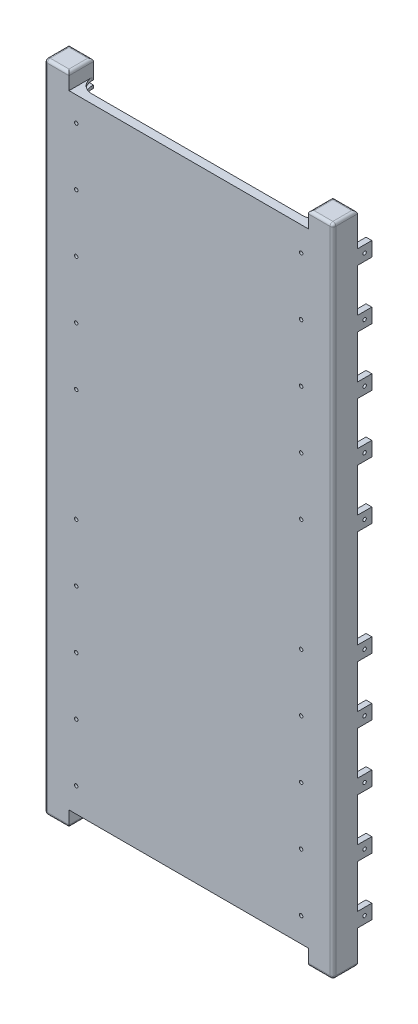
SolidWorks part; units mm, degrees
ref_plane "Front Plane" through (0, 0, 0) normal (0, 0, 1) x (1, 0, 0)
ref_plane "Top Plane" through (0, 0, 0) normal (0, 1, 0) x (1, 0, 0)
ref_plane "Right Plane" through (0, 0, 0) normal (1, 0, 0) x (0, 0, -1)
sketch "Sketch1" plane through (0, 0, 0) normal (0, 1, 0) x (1, 0, 0)
  line L1 (-3.25, -4.25) -> (4.25, -4.25)
  line L2 (-4.25, -3.25) -> (-4.25, 4.25)
  line L3 (-4.25, 4.25) -> (4.25, 4.25)
  line L4 (4.25, -4.25) -> (4.25, 4.25)
  line L5 (-4.25, -4.25) -> (4.25, 4.25) construction
  line L6 (-4.25, 4.25) -> (4.25, -4.25) construction
  arc A0 (-3.25, -4.25) -> (-4.25, -3.25) centre (-3.25, -3.25) cw
  point P0 (0, 0)
  dimension "D2" = 1
  dimension "D1" = 8.5
extrude "Boss-Extrude1" add sketch "Sketch1" along normal blind 227
ref_plane "Plane2" through (45.75, 0, 0) normal (-1, 0, 0) x (0, 0, 1)
ref_plane "Plane3" through (0, 113.5, 0) normal (0, 1, 0) x (1, 0, 0)
fillet "Fillet1" radius 1 10 edges at (0, 0, -4.25) (-4.25, 0, -0.5) (-3.9571, 0, 3.9571) (0.5, 0, 4.25) (4.25, 0, 0) (0.5, 227, 4.25) (-3.9571, 227, 3.9571) (-4.25, 227, -0.5) (0, 227, -4.25) (4.25, 227, 0)
ref_plane "Plane1" through (0, 0, 0) normal (-0.7071, 0, -0.7071) x (-0.7071, 0, 0.7071)
sketch "Sketch2" plane through (4.25, 0, 0) normal (1, 0, 0) x (0, 0, -1)
  line L0 (-4.25, 226) -> (-4.25, 1) construction
  line L1 (-4.25, 215.5) -> (-2.25, 215.5)
  line L2 (-4.25, 215.5) -> (-4.25, 210.5)
  line L3 (-4.25, 210.5) -> (-2.25, 210.5)
  line L4 (-2.25, 215.5) -> (-2.25, 210.5)
  line L5 (-3.25, 227) -> (3.25, 227) construction
  line L6 (-4.25, 195.5) -> (-2.25, 195.5)
  line L8 (-4.25, 195.5) -> (-4.25, 190.5)
  line L9 (-4.25, 190.5) -> (-2.25, 190.5)
  line L10 (-2.25, 195.5) -> (-2.25, 190.5)
  line L11 (-4.25, 175.5) -> (-2.25, 175.5)
  line L12 (-4.25, 175.5) -> (-4.25, 170.5)
  line L13 (-4.25, 170.5) -> (-2.25, 170.5)
  line L14 (-2.25, 175.5) -> (-2.25, 170.5)
  line L15 (-4.25, 155.5) -> (-2.25, 155.5)
  line L16 (-4.25, 155.5) -> (-4.25, 150.5)
  line L17 (-4.25, 150.5) -> (-2.25, 150.5)
  line L18 (-2.25, 155.5) -> (-2.25, 150.5)
  line L19 (-4.25, 135.5) -> (-2.25, 135.5)
  line L20 (-4.25, 135.5) -> (-4.25, 130.5)
  line L21 (-4.25, 130.5) -> (-2.25, 130.5)
  line L22 (-2.25, 135.5) -> (-2.25, 130.5)
  line L27 (-4.25, 120.5) -> (4.25, 120.5) construction
  line L28 (4.25, 226) -> (4.25, 1) construction
  line L29 (-4.25, 220.5) -> (4.25, 220.5) construction
  line L30 (-4.25, 113.5) -> (4.25, 113.5) construction
  line L35 (-2.25, 91.5) -> (-2.25, 96.5)
  line L36 (-4.25, 96.5) -> (-2.25, 96.5)
  line L37 (-4.25, 91.5) -> (-4.25, 96.5)
  line L38 (-4.25, 91.5) -> (-2.25, 91.5)
  line L39 (-2.25, 71.5) -> (-2.25, 76.5)
  line L40 (-4.25, 76.5) -> (-2.25, 76.5)
  line L41 (-4.25, 71.5) -> (-4.25, 76.5)
  line L42 (-4.25, 71.5) -> (-2.25, 71.5)
  line L43 (-2.25, 51.5) -> (-2.25, 56.5)
  line L44 (-4.25, 56.5) -> (-2.25, 56.5)
  line L45 (-4.25, 51.5) -> (-4.25, 56.5)
  line L46 (-4.25, 51.5) -> (-2.25, 51.5)
  line L47 (-2.25, 31.5) -> (-2.25, 36.5)
  line L48 (-4.25, 36.5) -> (-2.25, 36.5)
  line L49 (-4.25, 31.5) -> (-4.25, 36.5)
  line L50 (-4.25, 31.5) -> (-2.25, 31.5)
  line L51 (-2.25, 11.5) -> (-2.25, 16.5)
  line L52 (-4.25, 16.5) -> (-2.25, 16.5)
  line L53 (-4.25, 11.5) -> (-4.25, 16.5)
  line L54 (-4.25, 11.5) -> (-2.25, 11.5)
  line L55 (-4.25, 115.5) -> (-2.25, 115.5) [skipped]
  line L56 (-4.25, 115.5) -> (-4.25, 110.5) [skipped]
  line L57 (-2.25, 115.5) -> (-2.25, 110.5) [skipped]
  line L58 (-4.25, 110.5) -> (-2.25, 110.5) [skipped]
  dimension "D1" = 2
  dimension "D2" = 100
  dimension "D3" = 5
  dimension "D4" = 6
  dimension "D5" = 20
  dimension "D6" = 6.5
  dimension "D7" = 5
extrude "Boss-Extrude2" add sketch "Sketch2" along normal blind 5
sketch "Sketch13" plane through (4.25, 0, 0) normal (-1, 0, 0) x (0, 0, 1)
  line L1 (4.25, 220.5) -> (4.05, 220.5)
  line L2 (4.25, 220.5) -> (4.25, 6.5)
  line L3 (4.25, 6.5) -> (4.05, 6.5)
  line L4 (4.05, 220.5) -> (4.05, 6.5)
  line L6 (3.25, 227) -> (-3.25, 227) construction
  line L7 (-3.25, 0) -> (3.25, 0) construction
  dimension "D1" = 0.2
  dimension "D2" = 6.5
  dimension "D3" = 6.5
extrude "Boss-Extrude6" add sketch "Sketch13" along normal up to surface (41.5 mm away)
hole_wizard "#0-80 Tapped Hole1" positions "Sketch12" profile "Sketch11" tap size "#0-80" standard "ANSI Inch"
sketch "Sketch12" plane through (0, 0, 4.25) normal (0, 0, 1) x (1, 0, 0)
  line L0 (9.25, 215.5) -> (4.25, 215.5) construction
  line L2 (9.25, 215.5) -> (9.25, 210.5) construction
  line L5 (4.25, 113.5) -> (-3.25, 113.5) construction
  line L7 (-3.25, 226) -> (-3.25, 1) construction
  line L8 (4.25, 130.5) -> (4.25, 96.5) construction
  point P0 (6.75, 213)
  point P23 (6.75, 193)
  point P24 (6.75, 173)
  point P25 (6.75, 153)
  point P26 (6.75, 133)
  point P40 (6.75, 94)
  point P41 (6.75, 74)
  point P42 (6.75, 54)
  point P43 (6.75, 34)
  point P44 (6.75, 14)
  dimension "D1" = 2.5
  dimension "D2" = 2.5
  dimension "D4" = 20
  dimension "D3" = 5
sketch "Sketch11" plane through (6.75, 213, 4.25) normal (1, 0, 0) x (0, -1, 0)
  line L0 (0, 0) -> (0, 4.3584)
  line L1 (0, 4.3584) -> (0.5956, 4.0005)
  line L2 (0.5956, 4.0005) -> (0.5956, 0)
  line L5 (0.5956, 0) -> (0, 0)
  line L10 (0, 4.3584) -> (-0.5956, 4.0005) construction
  line L11 (0, -6.35) -> (0, 107.95) construction
  dimension "Tap Drill Dia." = 1.1913
  dimension "Tap Drill Depth" = 4.0005
  dimension "Drill Angle" = 118
cosmetic thread "Hole Thread1" parameters "D1"=2, "D2"=1.524
cosmetic thread "Hole Thread2" parameters "D1"=2, "D2"=1.524
cosmetic thread "Hole Thread11" parameters "D1"=2, "D2"=1.524
cosmetic thread "Hole Thread12" parameters "D1"=2, "D2"=1.524
cosmetic thread "Hole Thread13" parameters "D1"=2, "D2"=1.524
cosmetic thread "Hole Thread14" parameters "D1"=2, "D2"=1.524
cosmetic thread "Hole Thread15" parameters "D1"=2, "D2"=1.524
cosmetic thread "Hole Thread16" parameters "D1"=2, "D2"=1.524
cosmetic thread "Hole Thread17" parameters "D1"=2, "D2"=1.524
cosmetic thread "Hole Thread18" parameters "D1"=2, "D2"=1.524
fillet "Fillet2" radius 2.5 20 edges at (9.25, 215.5, 3.15) (9.25, 195.5, 3.15) (9.25, 175.5, 3.15) (9.25, 155.5, 3.15) (9.25, 135.5, 3.15) (9.25, 91.5, 3.15) (9.25, 71.5, 3.15) (9.25, 51.5, 3.15) (9.25, 31.5, 3.15) (9.25, 11.5, 3.15) (4.25, 215.5, 3.15) (4.25, 195.5, 3.15) (4.25, 175.5, 3.15) (4.25, 155.5, 3.15) (4.25, 135.5, 3.15) (4.25, 91.5, 3.15) (4.25, 71.5, 3.15) (4.25, 51.5, 3.15) (4.25, 11.5, 3.15) (4.25, 31.5, 3.15)
mirror "Mirror1" about plane through (0, 0, 0) normal (-0.7071, 0, -0.7071) of "#0-80 Tapped Hole1", "Boss-Extrude2"
sketch "Sketch3" plane through (0, 227, 0) normal (0, 1, 0) x (1, 0, 0)
  line L1 (-2.25, -2.25) -> (4.25, -2.25)
  line L2 (-2.25, -2.25) -> (-2.25, 4.25)
  line L3 (-2.25, 4.25) -> (4.25, 4.25)
  line L4 (4.25, -2.25) -> (4.25, 4.25)
  line L6 (4.25, -4.25) -> (-3.25, -4.25) construction
  line L7 (-4.25, -3.25) -> (-4.25, 4.25) construction
  dimension "D1" = 2
  dimension "D2" = 2
extrude "Cut-Extrude1" cut sketch "Sketch3" against normal offset from surface (214 mm away) 6.5 from offset 6.5 up to face at (0, 0, 0) offset against normal yes
mirror "Mirror7" about plane through (45.75, 0, 0) normal (-1, 0, 0) of "Fillet2", "Boss-Extrude1", "Fillet1", "Boss-Extrude2", "Boss-Extrude6", "#0-80 Tapped Hole1", "Mirror1", "Cut-Extrude1"
sketch "Sketch14" plane through (-2.25, 0, 0) normal (1, 0, 0) x (0, 0, -1)
  line L0 (-2.25, 6.5) -> (-2.25, 220.5) construction
  line L1 (-4.25, 8.05) -> (4.25, 8.05)
  line L2 (-4.25, 8.05) -> (-4.25, 9.05)
  line L3 (-4.25, 9.05) -> (4.25, 9.05)
  line L4 (4.25, 8.05) -> (4.25, 9.05)
  line L5 (4.25, 6.5) -> (4.25, 11.5) construction
  line L6 (4.25, 6.5) -> (-2.25, 6.5) construction
  line L7 (-4.25, 18.05) -> (4.25, 18.05)
  line L8 (-4.25, 6.5) -> (4.25, 6.5)
  line L9 (-4.25, 6.5) -> (-4.25, 5.5)
  line L10 (-4.25, 5.5) -> (4.25, 5.5)
  line L11 (4.25, 6.5) -> (4.25, 5.5)
  line L12 (-4.25, 18.05) -> (-4.25, 19.05)
  line L13 (-4.25, 19.05) -> (4.25, 19.05)
  line L14 (4.25, 18.05) -> (4.25, 19.05)
  line L15 (-4.25, 16.5) -> (4.25, 16.5)
  line L16 (-4.25, 16.5) -> (-4.25, 15.5)
  line L17 (-4.25, 15.5) -> (4.25, 15.5)
  line L18 (4.25, 16.5) -> (4.25, 15.5)
  line L19 (-4.25, 28.05) -> (4.25, 28.05)
  line L20 (-4.25, 28.05) -> (-4.25, 29.05)
  line L21 (-4.25, 29.05) -> (4.25, 29.05)
  line L22 (4.25, 28.05) -> (4.25, 29.05)
  line L23 (-4.25, 26.5) -> (4.25, 26.5)
  line L24 (-4.25, 26.5) -> (-4.25, 25.5)
  line L25 (-4.25, 25.5) -> (4.25, 25.5)
  line L26 (4.25, 26.5) -> (4.25, 25.5)
  line L27 (-4.25, 38.05) -> (4.25, 38.05)
  line L28 (-4.25, 38.05) -> (-4.25, 39.05)
  line L29 (-4.25, 39.05) -> (4.25, 39.05)
  line L30 (4.25, 38.05) -> (4.25, 39.05)
  line L31 (-4.25, 36.5) -> (4.25, 36.5)
  line L32 (-4.25, 36.5) -> (-4.25, 35.5)
  line L33 (-4.25, 35.5) -> (4.25, 35.5)
  line L34 (4.25, 36.5) -> (4.25, 35.5)
  line L35 (-4.25, 48.05) -> (4.25, 48.05)
  line L36 (-4.25, 48.05) -> (-4.25, 49.05)
  line L37 (-4.25, 49.05) -> (4.25, 49.05)
  line L38 (4.25, 48.05) -> (4.25, 49.05)
  line L39 (-4.25, 46.5) -> (4.25, 46.5)
  line L40 (-4.25, 46.5) -> (-4.25, 45.5)
  line L41 (-4.25, 45.5) -> (4.25, 45.5)
  line L42 (4.25, 46.5) -> (4.25, 45.5)
  line L43 (-4.25, 58.05) -> (4.25, 58.05)
  line L44 (-4.25, 58.05) -> (-4.25, 59.05)
  line L45 (-4.25, 59.05) -> (4.25, 59.05)
  line L46 (4.25, 58.05) -> (4.25, 59.05)
  line L47 (-4.25, 56.5) -> (4.25, 56.5)
  line L48 (-4.25, 56.5) -> (-4.25, 55.5)
  line L49 (-4.25, 55.5) -> (4.25, 55.5)
  line L50 (4.25, 56.5) -> (4.25, 55.5)
  line L51 (-4.25, 68.05) -> (4.25, 68.05)
  line L52 (-4.25, 68.05) -> (-4.25, 69.05)
  line L53 (-4.25, 69.05) -> (4.25, 69.05)
  line L54 (4.25, 68.05) -> (4.25, 69.05)
  line L55 (-4.25, 66.5) -> (4.25, 66.5)
  line L56 (-4.25, 66.5) -> (-4.25, 65.5)
  line L57 (-4.25, 65.5) -> (4.25, 65.5)
  line L58 (4.25, 66.5) -> (4.25, 65.5)
  line L59 (-4.25, 78.05) -> (4.25, 78.05)
  line L60 (-4.25, 78.05) -> (-4.25, 79.05)
  line L61 (-4.25, 79.05) -> (4.25, 79.05)
  line L62 (4.25, 78.05) -> (4.25, 79.05)
  line L63 (-4.25, 76.5) -> (4.25, 76.5)
  line L64 (-4.25, 76.5) -> (-4.25, 75.5)
  line L65 (-4.25, 75.5) -> (4.25, 75.5)
  line L66 (4.25, 76.5) -> (4.25, 75.5)
  line L67 (-4.25, 88.05) -> (4.25, 88.05)
  line L68 (-4.25, 88.05) -> (-4.25, 89.05)
  line L69 (-4.25, 89.05) -> (4.25, 89.05)
  line L70 (4.25, 88.05) -> (4.25, 89.05)
  line L71 (-4.25, 86.5) -> (4.25, 86.5)
  line L72 (-4.25, 86.5) -> (-4.25, 85.5)
  line L73 (-4.25, 85.5) -> (4.25, 85.5)
  line L74 (4.25, 86.5) -> (4.25, 85.5)
  line L75 (-4.25, 98.05) -> (4.25, 98.05)
  line L76 (-4.25, 98.05) -> (-4.25, 99.05)
  line L77 (-4.25, 99.05) -> (4.25, 99.05)
  line L78 (4.25, 98.05) -> (4.25, 99.05)
  line L79 (-4.25, 96.5) -> (4.25, 96.5)
  line L80 (-4.25, 96.5) -> (-4.25, 95.5)
  line L81 (-4.25, 95.5) -> (4.25, 95.5)
  line L82 (4.25, 96.5) -> (4.25, 95.5)
  line L83 (-4.25, 108.05) -> (4.25, 108.05)
  line L84 (-4.25, 108.05) -> (-4.25, 109.05)
  line L85 (-4.25, 109.05) -> (4.25, 109.05)
  line L86 (4.25, 108.05) -> (4.25, 109.05)
  line L87 (-4.25, 106.5) -> (4.25, 106.5)
  line L88 (-4.25, 106.5) -> (-4.25, 105.5)
  line L89 (-4.25, 105.5) -> (4.25, 105.5)
  line L90 (4.25, 106.5) -> (4.25, 105.5)
  line L91 (4.25, 96.5) -> (4.25, 130.5) construction
  line L92 (4.25, 113.5) -> (-2.25, 113.5) construction
  line L93 (4.25, 120.5) -> (4.25, 121.5)
  line L94 (-4.25, 121.5) -> (4.25, 121.5)
  line L95 (-4.25, 120.5) -> (-4.25, 121.5)
  line L96 (-4.25, 120.5) -> (4.25, 120.5)
  line L97 (4.25, 118.95) -> (4.25, 117.95)
  line L98 (-4.25, 117.95) -> (4.25, 117.95)
  line L99 (-4.25, 118.95) -> (-4.25, 117.95)
  line L100 (-4.25, 118.95) -> (4.25, 118.95)
  line L101 (4.25, 130.5) -> (4.25, 131.5)
  line L102 (-4.25, 131.5) -> (4.25, 131.5)
  line L103 (-4.25, 130.5) -> (-4.25, 131.5)
  line L104 (-4.25, 130.5) -> (4.25, 130.5)
  line L105 (4.25, 128.95) -> (4.25, 127.95)
  line L106 (-4.25, 127.95) -> (4.25, 127.95)
  line L107 (-4.25, 128.95) -> (-4.25, 127.95)
  line L108 (-4.25, 128.95) -> (4.25, 128.95)
  line L109 (4.25, 140.5) -> (4.25, 141.5)
  line L110 (-4.25, 141.5) -> (4.25, 141.5)
  line L111 (-4.25, 140.5) -> (-4.25, 141.5)
  line L112 (-4.25, 140.5) -> (4.25, 140.5)
  line L113 (4.25, 138.95) -> (4.25, 137.95)
  line L114 (-4.25, 137.95) -> (4.25, 137.95)
  line L115 (-4.25, 138.95) -> (-4.25, 137.95)
  line L116 (-4.25, 138.95) -> (4.25, 138.95)
  line L117 (4.25, 150.5) -> (4.25, 151.5)
  line L118 (-4.25, 151.5) -> (4.25, 151.5)
  line L119 (-4.25, 150.5) -> (-4.25, 151.5)
  line L120 (-4.25, 150.5) -> (4.25, 150.5)
  line L121 (4.25, 148.95) -> (4.25, 147.95)
  line L122 (-4.25, 147.95) -> (4.25, 147.95)
  line L123 (-4.25, 148.95) -> (-4.25, 147.95)
  line L124 (-4.25, 148.95) -> (4.25, 148.95)
  line L125 (4.25, 160.5) -> (4.25, 161.5)
  line L126 (-4.25, 161.5) -> (4.25, 161.5)
  line L127 (-4.25, 160.5) -> (-4.25, 161.5)
  line L128 (-4.25, 160.5) -> (4.25, 160.5)
  line L129 (4.25, 158.95) -> (4.25, 157.95)
  line L130 (-4.25, 157.95) -> (4.25, 157.95)
  line L131 (-4.25, 158.95) -> (-4.25, 157.95)
  line L132 (-4.25, 158.95) -> (4.25, 158.95)
  line L133 (4.25, 170.5) -> (4.25, 171.5)
  line L134 (-4.25, 171.5) -> (4.25, 171.5)
  line L135 (-4.25, 170.5) -> (-4.25, 171.5)
  line L136 (-4.25, 170.5) -> (4.25, 170.5)
  line L137 (4.25, 168.95) -> (4.25, 167.95)
  line L138 (-4.25, 167.95) -> (4.25, 167.95)
  line L139 (-4.25, 168.95) -> (-4.25, 167.95)
  line L140 (-4.25, 168.95) -> (4.25, 168.95)
  line L141 (4.25, 180.5) -> (4.25, 181.5)
  line L142 (-4.25, 181.5) -> (4.25, 181.5)
  line L143 (-4.25, 180.5) -> (-4.25, 181.5)
  line L144 (-4.25, 180.5) -> (4.25, 180.5)
  line L145 (4.25, 178.95) -> (4.25, 177.95)
  line L146 (-4.25, 177.95) -> (4.25, 177.95)
  line L147 (-4.25, 178.95) -> (-4.25, 177.95)
  line L148 (-4.25, 178.95) -> (4.25, 178.95)
  line L149 (4.25, 190.5) -> (4.25, 191.5)
  line L150 (-4.25, 191.5) -> (4.25, 191.5)
  line L151 (-4.25, 190.5) -> (-4.25, 191.5)
  line L152 (-4.25, 190.5) -> (4.25, 190.5)
  line L153 (4.25, 188.95) -> (4.25, 187.95)
  line L154 (-4.25, 187.95) -> (4.25, 187.95)
  line L155 (-4.25, 188.95) -> (-4.25, 187.95)
  line L156 (-4.25, 188.95) -> (4.25, 188.95)
  line L157 (4.25, 200.5) -> (4.25, 201.5)
  line L158 (-4.25, 201.5) -> (4.25, 201.5)
  line L159 (-4.25, 200.5) -> (-4.25, 201.5)
  line L160 (-4.25, 200.5) -> (4.25, 200.5)
  line L161 (4.25, 198.95) -> (4.25, 197.95)
  line L162 (-4.25, 197.95) -> (4.25, 197.95)
  line L163 (-4.25, 198.95) -> (-4.25, 197.95)
  line L164 (-4.25, 198.95) -> (4.25, 198.95)
  line L165 (4.25, 210.5) -> (4.25, 211.5)
  line L166 (-4.25, 211.5) -> (4.25, 211.5)
  line L167 (-4.25, 210.5) -> (-4.25, 211.5)
  line L168 (-4.25, 210.5) -> (4.25, 210.5)
  line L169 (4.25, 208.95) -> (4.25, 207.95)
  line L170 (-4.25, 207.95) -> (4.25, 207.95)
  line L171 (-4.25, 208.95) -> (-4.25, 207.95)
  line L172 (4.25, 220.5) -> (4.25, 221.5)
  line L173 (-4.25, 221.5) -> (4.25, 221.5)
  line L174 (-4.25, 220.5) -> (-4.25, 221.5)
  line L175 (-4.25, 220.5) -> (4.25, 220.5)
  line L176 (-4.25, 208.95) -> (4.25, 208.95)
  line L177 (4.25, 218.95) -> (4.25, 217.95)
  line L178 (-4.25, 217.95) -> (4.25, 217.95)
  line L179 (-4.25, 218.95) -> (-4.25, 217.95)
  line L180 (-4.25, 218.95) -> (4.25, 218.95)
  dimension "D1" = 1
  dimension "D2" = 1.55
  dimension "D4" = 10
  dimension "D5" = 8.5
  dimension "D3" = 11
extrude "Boss-Extrude7" add sketch "Sketch14" along normal up to surface (96 mm away)
sketch "Sketch15" plane through (0, 5.5, 0) normal (0, -1, 0) x (1, 0, 0)
  line L0 (4.25, -4.25) -> (4.25, -3.75)
  line L2 (4.25, -4.25) -> (87.25, -4.25)
  line L3 (87.25, -4.25) -> (87.25, -3.75)
  line L4 (87.25, -4.25) -> (87.25, 4.25) construction
  line L5 (4.25, 4.25) -> (4.25, -4.25) construction
  line L6 (9.25, 1.25) -> (82.25, 1.25)
  line L7 (87.25, 4.25) -> (4.25, 4.25) construction
  arc A0 (4.25, -3.75) -> (9.25, 1.25) centre (9.25, -3.75) cw
  arc A1 (87.25, -3.75) -> (82.25, 1.25) centre (82.25, -3.75) ccw
  point P14 (4.25, 1.25)
  point P17 (87.25, 1.25)
  dimension "D2" = 5
  dimension "D1" = 3
extrude "Cut-Extrude2" cut sketch "Sketch15" against normal through all
